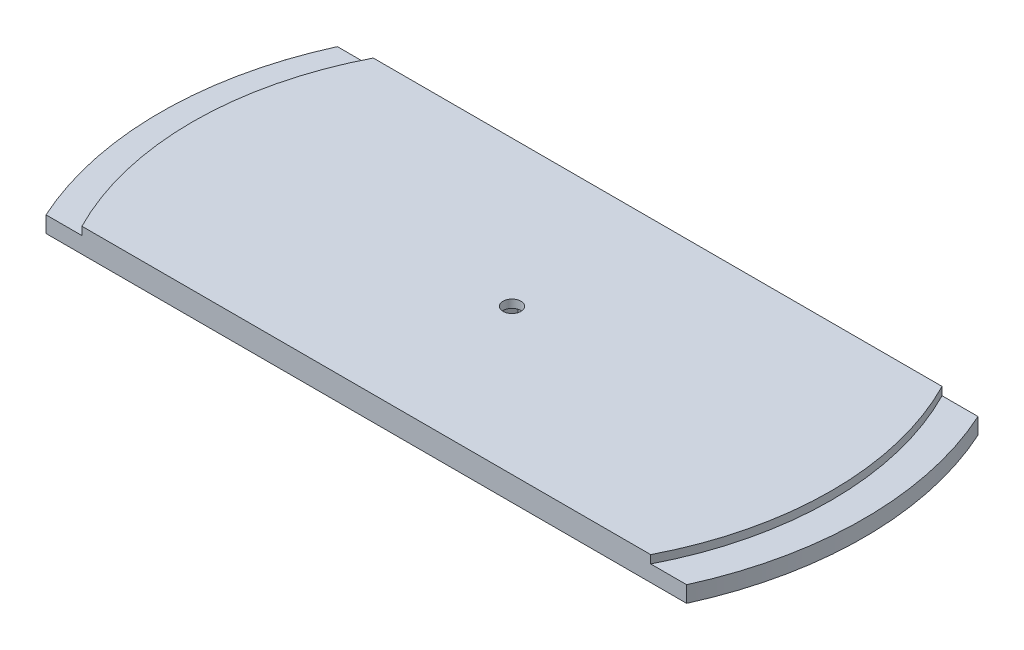
SolidWorks part; units mm, degrees
ref_plane "Front Plane" through (0, 0, 0) normal (0, 0, 1) x (1, 0, 0)
ref_plane "Top Plane" through (0, 0, 0) normal (0, 1, 0) x (1, 0, 0)
ref_plane "Right Plane" through (0, 0, 0) normal (1, 0, 0) x (0, 0, -1)
sketch "Sketch1" plane through (0, 0, 0) normal (0, 1, 0) x (1, 0, 0)
  line L2 (-125.6639, 57.15) -> (125.6639, 57.15)
  line L3 (-125.6639, -57.15) -> (125.6639, -57.15)
  line L4 (-6.5991, 0) -> (-3.2996, -5.715)
  line L5 (-3.2996, -5.715) -> (3.2996, -5.715)
  line L6 (3.2996, -5.715) -> (6.5991, 0)
  line L7 (6.5991, 0) -> (3.2996, 5.715)
  line L8 (3.2996, 5.715) -> (-3.2996, 5.715)
  line L9 (-3.2996, 5.715) -> (-6.5991, 0)
  arc A0 (-111.5628, 57.15) -> (-111.5628, -57.15) centre (0, 0) ccw
  arc A1 (-125.6639, 57.15) -> (-125.6639, -57.15) centre (0, 0) ccw
  circle A2 centre (0, 0) radius 5.715 construction
  circle A3 centre (0, 0) radius 3.4925
  arc A4 (125.6639, -57.15) -> (125.6639, 57.15) centre (0, 0) ccw
  arc A5 (111.5628, -57.15) -> (111.5628, 57.15) centre (0, 0) ccw
extrude "Boss-Extrude1" add sketch "Sketch1" along normal blind 9.525 contours L3 A5 L2 A0 L9 L8 L7 L6 L5 L4 region at (0, 0, -54.3948)
extrude "Boss-Extrude2" add sketch "Sketch1<3>" along normal blind 6.35 contours A5 L3 A4 L2 | L2 A1 L3 A0 region at (-127.3086, 0, 0) region at (127.3086, 0, 0)
sketch "Sketch1<3>" plane through (0, 0, 0) normal (0, 1, 0) x (1, 0, 0) same geometry as "Sketch1"
extrude "Boss-Extrude3" add sketch "Sketch1<4>" along normal blind 3.175 from offset 6.35 contours L8 L9 L4 L5 L6 L7 A3 region at (-4.7981, 0, -2.7702)
sketch "Sketch1<4>" plane through (0, 0, 0) normal (0, 1, 0) x (1, 0, 0) same geometry as "Sketch1"
